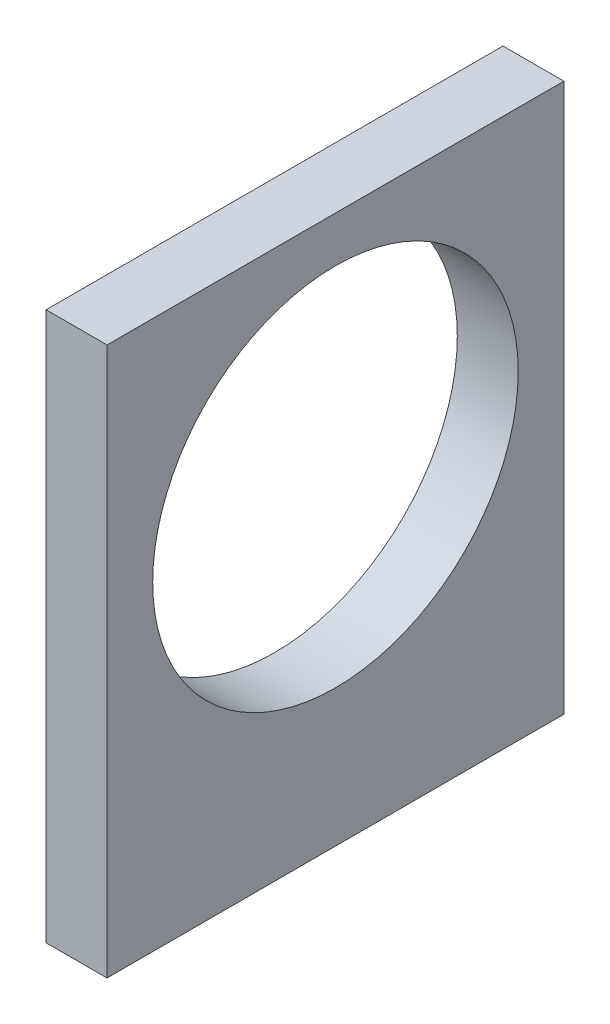
SolidWorks part; units mm, degrees
material "6061-T6 (SS)"
ref_plane "Front Plane" through (0, 0, 0) normal (0, 0, 1) x (1, 0, 0)
ref_plane "Top Plane" through (0, 0, 0) normal (0, 1, 0) x (1, 0, 0)
ref_plane "Right Plane" through (0, 0, 0) normal (1, 0, 0) x (0, 0, -1)
sketch "Sketch4" plane through (0, 0, 0) normal (1, 0, 0) x (0, 0, -1)
  line L0 (0, -14.2875) -> (0, -28.575) construction
  line L1 (23.8125, 28.575) -> (-23.8125, 28.575)
  line L2 (23.8125, 28.575) -> (23.8125, -28.575)
  line L3 (23.8125, -28.575) -> (-23.8125, -28.575)
  line L4 (-23.8125, 28.575) -> (-23.8125, -28.575)
  line L5 (23.8125, 28.575) -> (-23.8125, -28.575) construction
  line L6 (23.8125, -28.575) -> (-23.8125, 28.575) construction
  circle A0 centre (0, 4.7625) radius 19.05
  point P0 (0, 0)
  dimension "D3" = 38.1
  dimension "D1" = 14.2875
  dimension "D2" = 47.625
  dimension "D4" = 57.15
extrude "Boss-Extrude2" add sketch "Sketch4" along normal blind 6.35
sketch "Sketch5" plane through (0, 0, -23.8125) normal (0, 0, -1) x (-1, 0, 0)
  line L0 (-6.35, 28.575) -> (0, 28.575) construction
  line L1 (0, 28.575) -> (-3.175, 28.575)
  line L2 (0, 28.575) -> (0, -13.575)
  line L3 (0, -13.575) -> (-3.175, -13.575)
  line L4 (-3.175, 28.575) -> (-3.175, -13.575)
  dimension "D1" = 15
extrude "Cut-Extrude1" [suppressed] cut sketch "Sketch5" against normal through all
hole_wizard "Tap Drill for #6-32 Tap1" positions "Sketch6" profile "Sketch7" hole size "#6-32" standard "ANSI Inch"
sketch "Sketch6" plane through (0, -28.575, 0) normal (0, -1, 0) x (-1, 0, 0)
  line L3 (0, -23.8125) -> (0, 23.8125) construction
  line L4 (-6.35, 23.8125) -> (0, 23.8125) construction
  line L6 (-6.35, -23.8125) -> (0, -23.8125) construction
  point P0 (-3.175, 20.6375)
  point P2 (-3.175, -20.6375)
  point P28 (0, 0)
  dimension "D1" = 3.175
  dimension "D2" = 3.175
  dimension "D3" = 3.175
sketch "Sketch7" plane through (3.175, -28.575, -20.6375) normal (1, 0, 0) x (0, 0, -1)
  line L0 (0, 0) -> (0, 13.5127)
  line L1 (0, 13.5127) -> (1.3525, 12.7)
  line L2 (1.3525, 12.7) -> (1.3525, 0)
  line L5 (1.3525, 0) -> (0, 0)
  line L10 (0, 13.5127) -> (-1.3526, 12.7) construction
  line L11 (0, -6.35) -> (0, 107.95) construction
  dimension "Hole Dia." = 2.7051
  dimension "Hole Depth" = 12.7
  dimension "Drill Angle" = 118
